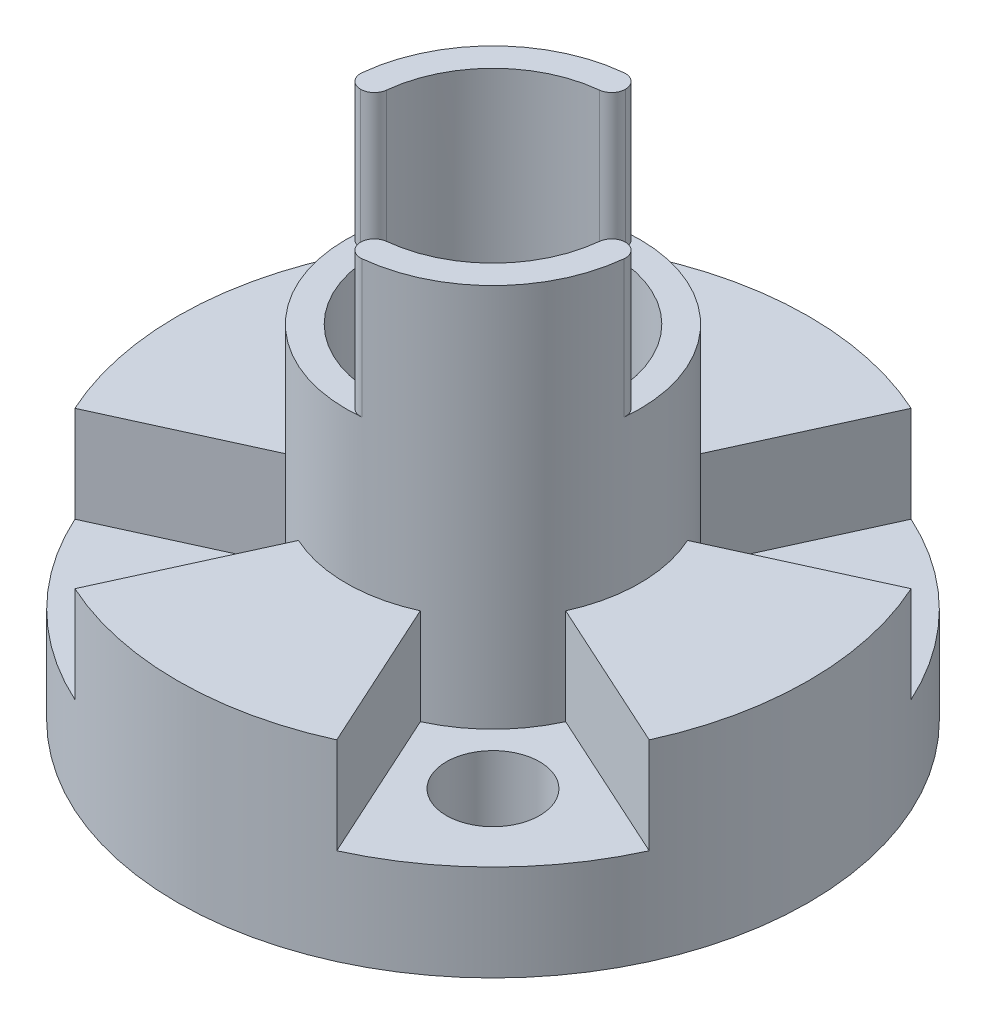
SolidWorks part; units mm, degrees
ref_plane "Alzado" through (0, 0, 0) normal (0, 0, 1) x (1, 0, 0)
ref_plane "Planta" through (0, 0, 0) normal (0, 1, 0) x (1, 0, 0)
ref_plane "Vista lateral" through (0, 0, 0) normal (1, 0, 0) x (0, 0, -1)
sketch "Croquis1" plane through (0, 0, 0) normal (0, 1, 0) x (1, 0, 0)
  line L0 (-8.3, -8.3) -> (8.3, 8.3) construction
  line L1 (-8.3, 8.3) -> (8.3, -8.3) construction
  circle A0 centre (0, 0) radius 4.35
  circle A1 centre (5.6569, 5.6569) radius 1.7
  circle A2 centre (-5.6569, 5.6569) radius 1.7
  circle A3 centre (-5.6569, -5.6569) radius 1.7
  circle A4 centre (5.6569, -5.6569) radius 1.7
  circle A5 centre (0, 0) radius 11.5
  dimension "D1" = 8.7
  dimension "D2" = 23
  dimension "D3" = 3.4
  dimension "D4" = 3.4
  dimension "D5" = 3.4
  dimension "D6" = 3.4
extrude "Saliente-Extruir1" add sketch "Croquis1" along normal blind 3.5
sketch "Croquis2" plane through (0, 3.5, 0) normal (0, 1, 0) x (1, 0, 0)
  circle A0 centre (0, 0) radius 4.35 construction
  circle A1 centre (0, 0) radius 4.35
  circle A2 centre (0, 0) radius 5.35
  dimension "D1" = 1
extrude "Saliente-Extruir2" add sketch "Croquis2" along normal blind 14
sketch "Croquis3" plane through (0, 17.5, 0) normal (0, 1, 0) x (1, 0, 0)
  line L0 (0, 5.35) -> (0, -5.35) construction
  line L1 (-5.35, 0) -> (5.35, 0) construction
  line L2 (0, 5.35) -> (0, 4.35)
  line L3 (5.35, 0) -> (4.35, 0)
  line L4 (0, -5.35) -> (0, -4.35)
  line L5 (-5.35, 0) -> (-4.35, 0)
  circle A0 centre (0, 0) radius 4.35 construction
  circle A1 centre (0, 0) radius 5.35 construction
  arc A2 (-4.35, 0) -> (0, -4.35) centre (0, 0) ccw
  arc A3 (-5.35, 0) -> (0, -5.35) centre (0, 0) ccw
  arc A4 (4.35, 0) -> (0, 4.35) centre (0, 0) ccw
  arc A5 (5.35, 0) -> (0, 5.35) centre (0, 0) ccw
extrude "Cortar-Extruir1" cut sketch "Croquis3" against normal blind 5
sketch "Croquis4" plane through (0, 0, 0) normal (0, -1, 0) x (1, 0, 0)
  circle A0 centre (0, 0) radius 4.35 construction
  circle A1 centre (0, 0) radius 4.35
  circle A2 centre (0, 0) radius 5.275
  dimension "D1" = 10.55
extrude "Cortar-Extruir2" cut sketch "Croquis4" against normal blind 2
fillet "Redondeo1" radius 0.6 1 edges at (0, 0, -5.275)
fillet "Redondeo2" radius 0.5 8 edges at (-4.35, 15, 0) (-5.35, 15, 0) (0, 15, 5.35) (0, 15, 4.35) (0, 15, -4.35) (0, 15, -5.35) (4.35, 15, 0) (5.35, 15, 0)
sketch "Croquis5" plane through (0, 3.5, 0) normal (0, 1, 0) x (1, 0, 0)
  line L0 (0, 11.5) -> (0, -11.5) construction
  line L1 (11.5, 0) -> (-11.5, 0) construction
  line L2 (0, 0) -> (-10.4635, 4.7713) construction
  line L3 (0, 0) -> (-10.4635, -4.7713) construction
  line L4 (0, 0) -> (10.4635, -4.7713) construction
  line L5 (0, 0) -> (10.4635, 4.7713) construction
  line L6 (0, 0) -> (-4.7713, 10.4635) construction
  line L7 (0, 0) -> (4.7713, 10.4635) construction
  line L8 (0, 0) -> (-4.7713, -10.4635) construction
  line L9 (0, 0) -> (4.7713, -10.4635) construction
  line L10 (-4.7713, 10.4635) -> (-2.2197, 4.8678)
  line L11 (4.7713, 10.4635) -> (2.2197, 4.8678)
  line L12 (10.4635, 4.7713) -> (4.8678, 2.2197)
  line L13 (10.4635, -4.7713) -> (4.8678, -2.2197)
  line L14 (4.7713, -10.4635) -> (2.2197, -4.8678)
  line L15 (-4.7713, -10.4635) -> (-2.2197, -4.8678)
  line L16 (-10.4635, -4.7713) -> (-4.8678, -2.2197)
  line L17 (-10.4635, 4.7713) -> (-4.8678, 2.2197)
  circle A0 centre (0, 0) radius 11.5 construction
  circle A1 centre (0, 0) radius 5.35 construction
  circle A2 centre (0, 0) radius 11.5
  arc A3 (2.2197, 4.8678) -> (-2.2197, 4.8678) centre (0, 0) ccw
  circle A5 centre (-5.6569, 5.6569) radius 1.7 construction
  circle A6 centre (-5.6569, -5.6569) radius 1.7 construction
  circle A7 centre (5.6569, -5.6569) radius 1.7 construction
  circle A8 centre (5.6569, 5.6569) radius 1.7 construction
  arc A9 (4.8678, -2.2197) -> (4.8678, 2.2197) centre (0, 0) ccw
  arc A10 (-2.2197, -4.8678) -> (2.2197, -4.8678) centre (0, 0) ccw
  arc A11 (-4.8678, 2.2197) -> (-4.8678, -2.2197) centre (0, 0) ccw
  circle M11 centre (0, 0) radius 11.5
  circle M14 centre (0, 0) radius 5.35
  dimension "D1" = 2.8
  dimension "D2" = 2.8
  dimension "D7" = 2.8
  dimension "D8" = 2.8
  dimension "D3" = 2.8
  dimension "D4" = 2.8
  dimension "D5" = 2.8
  dimension "D6" = 2.8
extrude "Saliente-Extruir3" add sketch "Croquis5" along normal blind 3.5 contours L17 L16 M11 M14 | L15 L14 M11 M14 | L13 L12 M11 M14 | L11 L10 M11 M14 region at (0, 3.5, -8.5331) region at (-8.5331, 3.5, 0) region at (8.5331, 3.5, 0) region at (0, 3.5, 8.5331)
